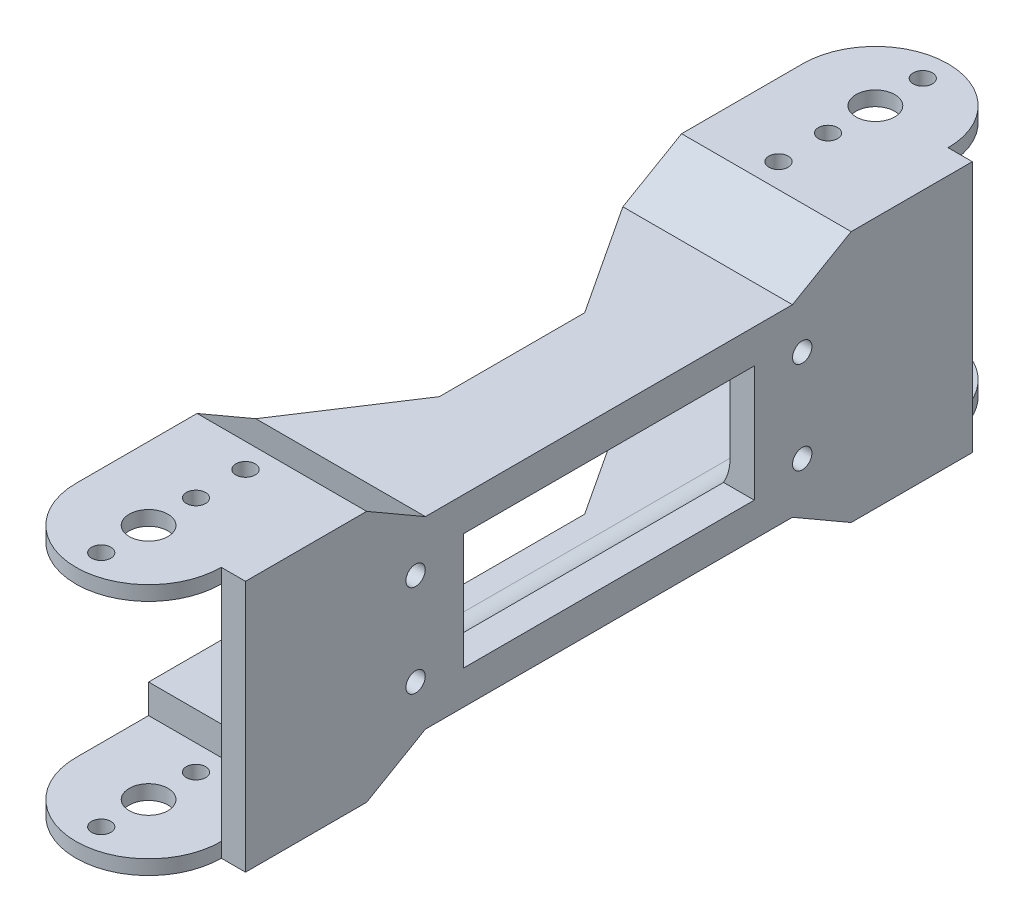
SolidWorks part; units mm, degrees
material "POM Acetal Copolymer"
ref_plane "Front Plane" through (0, 0, 0) normal (0, 0, 1) x (1, 0, 0)
ref_plane "Top Plane" through (0, 0, 0) normal (0, 1, 0) x (1, 0, 0)
ref_plane "Right Plane" through (0, 0, 0) normal (1, 0, 0) x (0, 0, -1)
sketch "Sketch1" plane through (0, 0, 0) normal (0, 1, 0) x (1, 0, 0)
  line L0 (0, 75) -> (0, -75) construction
  line L2 (-15, 75) -> (-15, -75)
  line L4 (15, 75) -> (15, -75)
  arc A0 (15, 75) -> (-15, 75) centre (0, 75) ccw
  arc A1 (-15, -75) -> (15, -75) centre (0, -75) ccw
  circle A2 centre (0, -55) radius 2
  point P5 (0, 0)
  dimension "D3" = 4
  dimension "D1" = 150
  dimension "D2" = 30
  dimension "D4" = 20
extrude "Boss-Extrude1" add sketch "Sketch1" along normal mid plane 52
sketch "Sketch3" plane through (-15, 0, 0) normal (-1, 0, 0) x (0, 0, 1)
  line L0 (-50, 26) -> (-37.8756, 19)
  line L1 (-75, 26) -> (75, 26) construction
  line L2 (-37.8756, 19) -> (37.8756, 19)
  line L3 (37.8756, 19) -> (50, 26)
  line L4 (50, 26) -> (-50, 26)
  line L5 (-75, 26) -> (-75, -26) construction
  point P6 (0, 19)
  point P7 (0, 26)
  dimension "D1" = 7
  dimension "D2" = 30
  dimension "D3" = 25
extrude "Cut-Extrude1" cut sketch "Sketch3" against normal through all both and the other way through all
mirror "Mirror1" about plane through (0, 0, 0) normal (0, 1, 0) of "Cut-Extrude1"
sketch "Sketch4" plane through (-15, 0, 0) normal (-1, 0, 0) x (0, 0, 1)
  line L0 (-90, 26) -> (-90, -26) construction
  line L1 (60, 23) -> (90, 23)
  line L2 (-90, 23) -> (-60, 23)
  line L3 (-90, 23) -> (-90, 17)
  line L4 (-90, 17) -> (-60, 17)
  line L5 (-60, 23) -> (-60, 17)
  line L6 (-90, -23) -> (-60, -23)
  line L7 (-90, -23) -> (-90, -17)
  line L8 (-90, -17) -> (-60, -17)
  line L9 (-60, -23) -> (-60, -17)
  line L10 (60, 23) -> (60, 17)
  line L11 (60, 17) -> (90, 17)
  line L12 (90, 23) -> (90, 17)
  line L13 (60, -17) -> (90, -17)
  line L14 (60, -17) -> (60, -23)
  line L15 (60, -23) -> (90, -23)
  line L16 (90, -17) -> (90, -23)
  line L18 (90, -26) -> (90, 26) construction
  line L19 (-60, 17) -> (-60, -17) construction
  line L20 (60, 17) -> (60, -17) construction
  point P20 (-60, 0)
  dimension "D1" = 30
  dimension "D2" = 6
  dimension "D3" = 34
extrude "Cut-Extrude2" cut sketch "Sketch4" against normal through all both
sketch "Sketch5" plane through (-15, 0, 0) normal (-1, 0, 0) x (0, 0, 1)
  line L1 (-90, 17) -> (90, 17)
  line L2 (-90, 17) -> (-90, -17)
  line L3 (-90, -17) -> (90, -17)
  line L4 (90, 17) -> (90, -17)
extrude "Cut-Extrude3" cut sketch "Sketch5" against normal offset from surface (25 mm away) 5 up to face at (15, 0, 0)
sketch "Sketch6" plane through (10, 0, 0) normal (-1, 0, 0) x (0, 0, 1)
  line L0 (60, -17) -> (-60, -17) construction
  line L1 (86.1803, 17) -> (60, 17)
  line L2 (86.1803, 17) -> (86.1803, -17)
  line L3 (86.1803, -17) -> (60, -17)
  line L4 (60, 17) -> (60, -17)
  line L5 (60, -17) -> (60, -23) construction
extrude "Cut-Extrude4" cut sketch "Sketch6" against normal through all
sketch "Sketch7" plane through (10, 0, 0) normal (-1, 0, 0) x (0, 0, 1)
  line L1 (-86.1803, 17) -> (-60, 17)
  line L2 (-86.1803, 17) -> (-86.1803, -17)
  line L3 (-86.1803, -17) -> (-60, -17)
  line L4 (-60, 17) -> (-60, -17)
extrude "Cut-Extrude5" cut sketch "Sketch7" against normal through all
hole_wizard "5/32 (0.15625) Diameter Hole1" positions "Sketch11" profile "Sketch12" hole size "5/32" standard "ANSI Inch"
sketch "Sketch11" plane through (0, 26, 0) normal (0, 1, 0) x (1, 0, 0)
  line L0 (9.779, -75) -> (-9.779, -75) construction
  line L2 (0, -65.221) -> (0, -84.779) construction
  arc A0 (-15, -75) -> (15, -75) centre (0, -75) ccw construction
  point P0 (0, -65.221)
  point P6 (0, -84.779)
  point P17 (0, -75)
  point P18 (0, -75)
  dimension "D1" = 19.558
sketch "Sketch12" plane through (0, 26, 65.221) normal (1, 0, 0) x (0, 0, 1)
  line L0 (0, 0) -> (0, 4.1923)
  line L1 (0, 4.1923) -> (1.9844, 3)
  line L2 (1.9844, 3) -> (1.9844, 0)
  line L5 (1.9844, 0) -> (0, 0)
  line L10 (0, 4.1923) -> (-1.9844, 3) construction
  line L11 (0, -6.35) -> (0, 107.95) construction
  dimension "Hole Dia." = 3.9688
  dimension "Hole Depth" = 3
  dimension "Drill Angle" = 118
mirror "Mirror5" about plane through (0, 0, 0) normal (0, 1, 0) of "5/32 (0.15625) Diameter Hole1"
mirror "Mirror3" about plane through (0, 0, 0) normal (0, 0, 1) of "5/32 (0.15625) Diameter Hole1"
sketch "Sketch13" plane through (0, -26, 0) normal (0, -1, 0) x (1, 0, 0)
  circle A0 centre (0, -75) radius 4
  arc A1 (-15, -75) -> (15, -75) centre (0, -75) ccw construction
  dimension "D1" = 8
extrude "Cut-Extrude6" cut sketch "Sketch13" against normal through all both and the other way through all
mirror "Mirror4" about plane through (0, 0, 0) normal (0, 0, 1) of "Cut-Extrude6"
sketch "Sketch14" plane through (15, 0, 0) normal (1, 0, 0) x (0, 0, -1)
  line L0 (-75, 26) -> (-75, 23)
  line L1 (-75, 23) -> (-60, 23)
  line L2 (-60, 23) -> (-60, -23)
  line L3 (-60, -23) -> (-75, -23)
  line L4 (-75, -23) -> (-75, -26)
  line L5 (-75, -26) -> (-50, -26)
  line L6 (-50, -26) -> (-37.8756, -19)
  line L7 (-37.8756, -19) -> (37.8756, -19)
  line L8 (37.8756, -19) -> (50, -26)
  line L12 (60, -23) -> (60, 23)
  line L13 (60, 23) -> (75, 23)
  line L14 (75, 23) -> (75, 26)
  line L15 (75, 26) -> (50, 26)
  line L16 (50, 26) -> (37.8756, 19)
  line L17 (37.8756, 19) -> (-37.8756, 19)
  line L18 (-37.8756, 19) -> (-50, 26)
  line L19 (-50, 26) -> (-75, 26)
  line L20 (60, -23) -> (75, -23)
  line L21 (75, -23) -> (75, -26)
  line L22 (75, -26) -> (50, -26)
extrude "Boss-Extrude2" add sketch "Sketch14" along normal blind 5
sketch "Sketch15" plane through (10, 0, 0) normal (-1, 0, 0) x (0, 0, 1)
  line L1 (-60, 17) -> (60, 17)
  line L2 (-60, 17) -> (-60, -17)
  line L3 (-60, -17) -> (60, -17)
  line L4 (60, 17) -> (60, -17)
extrude "Cut-Extrude7" cut sketch "Sketch15" against normal blind 5
sketch "Sketch17" plane through (0, 0, 60) normal (0, 0, 1) x (1, 0, 0)
  line L0 (20, -26) -> (15, -26) construction
  line L1 (20, 26) -> (15, 26)
  line L2 (20, 26) -> (20, -26)
  line L3 (20, -26) -> (15, -26)
  line L4 (15, 26) -> (15, -26)
  line L5 (15, -17) -> (15, 17) construction
extrude "Boss-Extrude4" add sketch "Sketch17" along normal up to surface (15 mm away) up to face at (17.5, 24.5, 75)
mirror "Mirror6" about plane through (0, 0, 0) normal (0, 1, 0) of "Mirror3"
sketch "Sketch19" plane through (20, 0, 0) normal (1, 0, 0) x (0, 0, -1)
  line L0 (-39.899, 9.525) -> (-39.899, -9.525) construction
  line L3 (-75, 26) -> (-75, -26) construction
  circle A0 centre (-39.899, 9.525) radius 2
  circle A1 centre (-39.899, -9.525) radius 2
  point P4 (-39.899, 0)
  dimension "D2" = 4
  dimension "D1" = 19.05
  dimension "D3" = 35.101
extrude "Cut-Extrude11" cut sketch "Sketch19" against normal blind 10
sketch "Sketch18" plane through (0, 26, 0) normal (0, 1, 0) x (1, 0, 0)
  circle A0 centre (0, 55) radius 2
  circle A2 centre (0, 75) radius 4 construction
  dimension "D1" = 4
  dimension "D2" = 20
extrude "Cut-Extrude8" cut sketch "Sketch18" against normal up to surface (52 mm away) up to face at (0, -26, -67.2054)
sketch "Sketch20" plane through (15, 0, 0) normal (-1, 0, 0) x (0, 0, 1)
  line L1 (-30, 12) -> (30, 12)
  line L2 (-30, 12) -> (-30, -12)
  line L3 (-30, -12) -> (30, -12)
  line L4 (30, 12) -> (30, -12)
  point P4 (30, 0)
  point P8 (0, -12)
  dimension "D1" = 60
  dimension "D2" = 24
extrude "Cut-Extrude10" cut sketch "Sketch20" against normal blind 10
mirror "Mirror7" about plane through (0, 0, 0) normal (0, 0, 1) of "Cut-Extrude11"
sketch "Sketch21" plane through (0, 19, 0) normal (0, 1, 0) x (1, 0, 0)
  line L0 (-15, 37.8756) -> (0, 15)
  line L2 (0, 15) -> (0, -15)
  line L3 (0, -15) -> (-15, -37.8756)
  line L4 (-15, -37.8756) -> (-15, 37.8756)
  line L5 (20, 37.8756) -> (-15, 37.8756) construction
  point P4 (-15, 0)
  point P9 (0, 0)
  dimension "D1" = 30
extrude "Cut-Extrude12" cut sketch "Sketch21" against normal up to surface (38 mm away) up to face at (2.5, -19, 0)
sketch "Sketch22" plane through (0, 0, -60) normal (0, 0, -1) x (-1, 0, 0)
  line L1 (-20, 23) -> (-15, 23)
  line L2 (-20, 23) -> (-20, -23)
  line L3 (-20, -23) -> (-15, -23)
  line L4 (-15, 23) -> (-15, -23)
extrude "Boss-Extrude5" add sketch "Sketch22" along normal up to surface (15 mm away) up to face at (17.5, 24.5, -75)
fillet "Fillet1" radius 10 2 edges at (15, 17, 0) (15, -17, 0)
